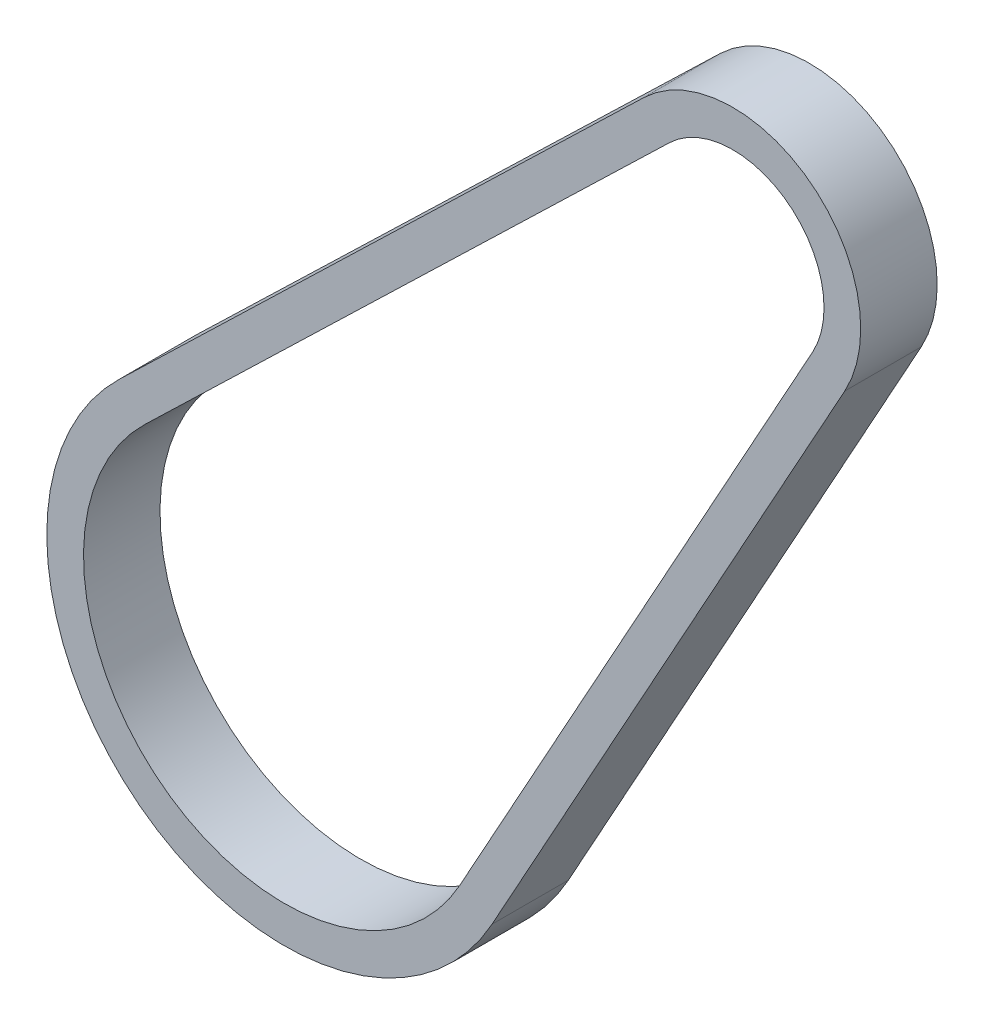
SolidWorks part; units mm, degrees
material "Rubber"
ref_plane "Front Plane" through (0, 0, 0) normal (0, 0, 1) x (1, 0, 0)
ref_plane "Top Plane" through (0, 0, 0) normal (0, 1, 0) x (1, 0, 0)
ref_plane "Right Plane" through (0, 0, 0) normal (1, 0, 0) x (0, 0, -1)
sketch "Sketch2" plane through (0, 0, 0) normal (0, 0, 1) x (1, 0, 0)
  line L0 (0, 0) -> (1, 0) construction
  line L1 (0, 0) -> (0, 1) construction
  line L2 (35.6051, 34.8001) -> (12.5359, -6.9301)
  line L3 (-9.9469, 10.307) -> (24.3637, 43.4187)
  arc A0 (24.3637, 43.4187) -> (35.6051, 34.8001) centre (29.3371, 38.2652) cw
  arc A1 (12.5359, -6.9301) -> (-9.9469, 10.307) centre (0, 0) cw
extrude "Extrude-Thin1" add sketch "Sketch2" against normal blind 5 thin thin type two direction wall 1.2 second wall 1.2
